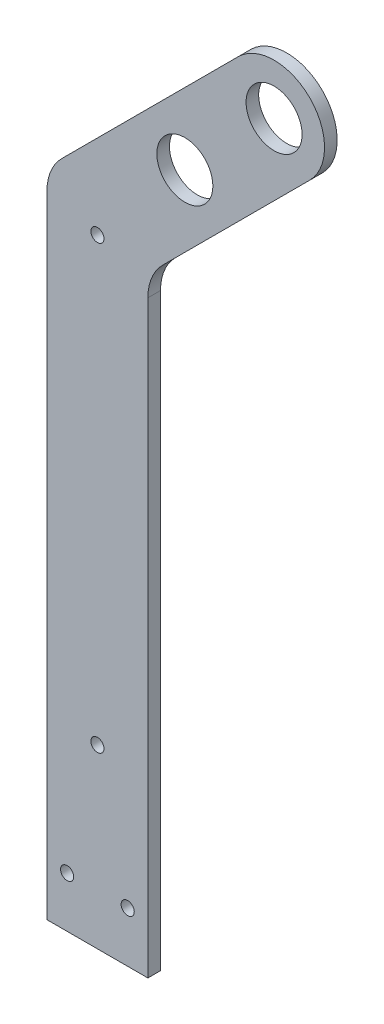
SolidWorks part; units mm, degrees
material "6061 合金"
ref_plane "前视基准面" through (0, 0, 0) normal (0, 0, 1) x (1, 0, 0)
ref_plane "上视基准面" through (0, 0, 0) normal (0, 1, 0) x (1, 0, 0)
ref_plane "右视基准面" through (0, 0, 0) normal (1, 0, 0) x (0, 0, -1)
other "Configuration Table"
sketch "草图1" plane through (0, 0, 0) normal (0, 0, 1) x (1, 0, 0)
  circle A0 centre (0, 0) radius 20
  circle A1 centre (0, 0) radius 11.1
  dimension "D1" = 40
  dimension "D2" = 22.2
extrude "凸台-拉伸1" add sketch "草图1" along normal blind 60 contours A1 | A0 region at (0, 0, 0)
ref_plane "基准面1" through (0, 0, 30) normal (0, 0, 1) x (1, 0, 0)
sketch "草图2" plane through (0, 0, 30) normal (0, 0, 1) x (1, 0, 0)
  line L0 (0, 0) -> (-70, -70) construction
  line L1 (-70, -70) -> (-70, -320) construction
  line L2 (0, -57.3148) -> (0, 49.9409) construction
  line L3 (-56.8582, 0) -> (46.4003, 0) construction
  line L4 (-14.1421, 14.1421) -> (-90, -61.7157)
  line L5 (14.1421, -14.1421) -> (-50, -78.2843)
  line L6 (-90, -61.7157) -> (-90, -320)
  line L7 (-50, -78.2843) -> (-50, -320)
  line L8 (-90, -320) -> (-50, -320)
  circle A2 centre (0, 0) radius 20 construction
  arc A3 (-14.1421, 14.1421) -> (14.1421, -14.1421) centre (0, 0) ccw
  dimension "D1" = 45
  dimension "D2" = 250
  dimension "D3" = 70
  dimension "D4" = 40
  dimension "D5" = 40
extrude "凸台-拉伸2" add sketch "草图2" along normal mid plane 60 contours L7 L8 L6 L4 A3 L5
sketch "草图4" plane through (0, 0, 60) normal (0, 0, 1) x (1, 0, 0)
  line L0 (-90, -61.7157) -> (-90, -320) construction
  line L1 (-90, -290) -> (-50, -290)
  line L2 (-90, -290) -> (-90, -350)
  line L4 (-50, -290) -> (-50, -350)
  line L5 (-50, -78.2843) -> (-50, -320) construction
  line L6 (-90, -320) -> (-50, -320) construction
  arc A0 (-90, -350) -> (-50, -350) centre (-70, -350) ccw
  circle A1 centre (-70, -350) radius 11
  dimension "D3" = 22
  dimension "D1" = 30
  dimension "D2" = 30
extrude "凸台-拉伸3" add sketch "草图4" along normal blind 5
mirror "镜向1" about plane through (0, 0, 30) normal (0, 0, 1) of "凸台-拉伸3"
sketch "草图5" plane through (0, 0, 0) normal (0, 1, 0) x (1, 0, 0)
  line L0 (0, 0) -> (0, -78.0582) construction
ref_plane "基准面2" through (-70, 0, 0) normal (-1, 0, 0) x (0, 0, 1)
sketch "草图7" plane through (-70, 0, 0) normal (-1, 0, 0) x (0, 0, 1)
  line L0 (-34.1239, -350) -> (109.535, -350) construction
sketch "草图8" plane through (0, 0, 60) normal (0, 0, 1) x (1, 0, 0)
  line L0 (0, 0) -> (-70, -70) construction
  circle A0 centre (-35.3553, -35.3553) radius 11.1
  dimension "D1" = 22.2
  dimension "D2" = 50
extrude "切除-拉伸1" cut sketch "草图8" against normal blind 100
fillet "圆角4" radius 20 2 edges at (-90, -61.7157, 30) (-50, -78.2843, 30)
fillet "圆角1" [suppressed] radius 50
fillet "圆角2" [suppressed] radius 3
sketch "草图9" plane through (0, 0, 65) normal (0, 0, 1) x (1, 0, 0)
  circle A0 centre (-70, -350) radius 13
  dimension "D1" = 26
extrude "切除-拉伸2" [suppressed] cut sketch "草图9" against normal blind 0.75
sketch "草图10" plane through (0, 0, -5) normal (0, 0, -1) x (-1, 0, 0)
  circle A0 centre (70, -350) radius 13
  dimension "D1" = 26
extrude "切除-拉伸3" [suppressed] cut sketch "草图10" against normal blind 0.75 contours A0
sketch "草图11" plane through (-90, 0, 0) normal (-1, 0, 0) x (0, 0, 1)
  circle A0 centre (48.5, -118.9949) radius 2.75
  circle A1 centre (48.5, -183.9949) radius 2.75
  circle A2 centre (48.5, -248.9949) radius 2.75
  circle A3 centre (11.5, -248.9949) radius 2.75
  circle A4 centre (11.5, -183.9949) radius 2.75
  circle A5 centre (11.5, -118.9949) radius 2.75
  dimension "D1" = 5.5
extrude "切除-拉伸4" [suppressed] cut sketch "草图11" against normal through all contours A1 | A2 | A0 | A3 | A4 | A5
sketch "草图12" [suppressed] plane through (-90, 0, 0) normal (-1, 0, 0) x (0, 0, 1)
  line L0 (30, -62.0134) -> (30, -339.6946) construction
  line L1 (10, -128.9949) -> (50, -128.9949)
  line L2 (10, -128.9949) -> (10, -173.9949)
  line L3 (10, -173.9949) -> (50, -173.9949)
  line L4 (50, -128.9949) -> (50, -173.9949)
  line L5 (10, -193.9949) -> (50, -193.9949)
  line L6 (10, -193.9949) -> (10, -238.9949)
  line L7 (10, -238.9949) -> (50, -238.9949)
  line L8 (50, -193.9949) -> (50, -238.9949)
  line L9 (10, -258.9949) -> (50, -258.9949)
  line L10 (10, -258.9949) -> (10, -290)
  line L11 (10, -290) -> (50, -290)
  line L12 (50, -258.9949) -> (50, -290)
  line L13 (19.5, -173.9949) -> (40.5, -173.9949)
  line L14 (19.5, -173.9949) -> (19.5, -193.9949)
  line L15 (19.5, -193.9949) -> (40.5, -193.9949)
  line L16 (40.5, -173.9949) -> (40.5, -193.9949)
  line L17 (19.5, -238.9949) -> (40.5, -238.9949)
  line L18 (19.5, -238.9949) -> (19.5, -258.9949)
  line L19 (19.5, -258.9949) -> (40.5, -258.9949)
  line L20 (40.5, -238.9949) -> (40.5, -258.9949)
  line L21 (60, -82.4264) -> (60, -290) construction
  line L22 (0, -290) -> (0, -82.4264) construction
  line L23 (57, -320) -> (3, -320) construction
  circle A0 centre (48.5, -118.9949) radius 2.75 construction
  circle A1 centre (48.5, -183.9949) radius 2.75 construction
  circle A2 centre (48.5, -248.9949) radius 2.75 construction
  dimension "D1" = 10
  dimension "D2" = 10
  dimension "D3" = 10
  dimension "D4" = 8
  dimension "D5" = 10
  dimension "D6" = 10
  dimension "D7" = 10
  dimension "D8" = 30
extrude "减重" [suppressed] cut sketch "草图12" against normal through all contours L0 L1 L2 L3 | L15 L0 L17 L7 L8 L5 | L0 L5 L6 L7 | L19 L0 L11 L12 L9 | L0 L9 L10 L11 | L1 L0 L13 L3 L4
fillet "圆角3" [suppressed] radius 3
sketch "草图13" plane through (0, 0, 60) normal (0, 0, 1) x (1, 0, 0)
  circle A0 centre (0, 0) radius 13
  circle A1 centre (-35.3553, -35.3553) radius 13
  dimension "D1" = 26
  dimension "D2" = 26
extrude "切除-拉伸6" [suppressed] cut sketch "草图13" against normal blind 1.75
sketch "草图14" plane through (0, 0, 0) normal (0, 0, -1) x (-1, 0, 0)
  circle A0 centre (0, 0) radius 13
  circle A1 centre (35.3553, -35.3553) radius 13
  dimension "D1" = 26
  dimension "D2" = 26
extrude "切除-拉伸7" [suppressed] cut sketch "草图14" against normal blind 1.75
sketch "草图15" [suppressed] plane through (0, 0, 0) normal (0, 0, -1) x (-1, 0, 0)
  line L0 (0, 0) -> (70, -350) construction
  line L1 (56.2719, -67.2005) -> (60.1942, -86.8121) construction
  line L2 (70, -350) -> (204.3541, -323.1292) construction
  circle A0 centre (56.2719, -67.2005) radius 2.75
  circle A1 centre (75.2172, -73.6095) radius 2.75
  circle A2 centre (60.1942, -86.8121) radius 2.75
  dimension "D1" = 5.5
  dimension "D2" = 20
  dimension "D3" = 20
  dimension "D4" = 20
  dimension "D5" = 42
  dimension "D6" = 270
extrude "切除-拉伸8" [suppressed] cut sketch "草图15" against normal through all contours A2 | A0 | A1
ref_plane "小腿主干连杆面" through (0, 0, 0) normal (0.9806, -0.1961, 0) x (0, 0, -1)
ref_plane "小腿主干对称面" through (0, 0, 30) normal (0, 0, -1) x (-1, 0, 0)
sketch "草图16" plane through (0, 0, 60) normal (0, 0, 1) x (1, 0, 0)
  line L0 (0, 0) -> (-70, -350)
  line L1 (-35.3553, -35.3553) -> (0, 0)
sketch "草图17" plane through (0, 0, 60) normal (0, 0, 1) x (1, 0, 0)
  line L0 (0, 0) -> (-70, -350) construction
  line L1 (118.6974, 32.5948) -> (32.9122, -396.3312) construction
  line L2 (92.7764, -97.0102) -> (20.2919, -82.5133)
  line L3 (73.1648, -195.0683) -> (0.6803, -180.5713)
  circle A0 centre (20.2919, -82.5133) radius 46
  circle A1 centre (0.6803, -180.5713) radius 46
  dimension "D3" = 92
  dimension "D4" = 92
  dimension "D1" = 110
  dimension "D2" = 73.92
  dimension "D5" = 180
  dimension "D6" = 280
sketch "草图18" plane through (0, 0, 60) normal (0, 0, 1) x (1, 0, 0)
  line L1 (14.1421, -14.1421) -> (-44.1421, -72.4264) construction
  line L3 (14.1421, -14.1421) -> (-44.1421, -72.4264)
  line L4 (15.4873, -12.6548) -> (52.8188, -49.9864)
  line L5 (-50, -128.5133) -> (20.2919, -128.5133)
  line L10 (-90, -290) -> (-50, -290)
  line L11 (-50, -290) -> (-50, -86.5685)
  line L12 (-44.1421, -72.4264) -> (14.1421, -14.1421)
  line L13 (-14.1421, 14.1421) -> (-84.1421, -55.8579)
  line L14 (-90, -70) -> (-90, -290)
  line L16 (-50, -128.5133) -> (-50, -86.5685)
  line L17 (-44.1421, -72.4264) -> (14.1421, -14.1421)
  circle A0 centre (20.2919, -82.5133) radius 46 construction
  arc A1 (14.1421, -14.1421) -> (-14.1421, 14.1421) centre (0, 0) ccw construction
  arc A2 (14.1421, -14.1421) -> (-14.1421, 14.1421) centre (0, 0) ccw
  arc A3 (14.1421, -14.1421) -> (15.4873, -12.6548) centre (0, 0) ccw
  arc A4 (20.2919, -128.5133) -> (52.8188, -49.9864) centre (20.2919, -82.5133) ccw
  circle A5 centre (20.2919, -82.5133) radius 35
  arc A9 (-84.1421, -55.8579) -> (-90, -70) centre (-70, -70) ccw
  arc A10 (-84.1421, -55.8579) -> (-90, -70) centre (-70, -70) ccw
  arc A11 (-44.1421, -72.4264) -> (-50, -86.5685) centre (-30, -86.5685) ccw
  arc A12 (-44.1421, -72.4264) -> (-50, -86.5685) centre (-30, -86.5685) ccw
  line M14 (-50, -290) -> (-50, -86.5685)
  line M15 (-44.1421, -72.4264) -> (14.1421, -14.1421)
  arc M16 (14.1421, -14.1421) -> (-14.1421, 14.1421) centre (0, 0) ccw
  arc M22 (-50, -86.5685) -> (-44.1421, -72.4264) centre (-30, -86.5685) cw
  dimension "D2" = 70
  dimension "D1" = 0
extrude "凸台-拉伸4" add sketch "草图18" against normal blind 5 from offset 25 contours L5 A4 L4 A5 M16 M15 M22 M14 region at (16.0508, -14.5165, 60) offset against normal yes
sketch "草图19" plane through (0, 0, 0) normal (0, 0, -1) x (-1, 0, 0)
  line L0 (50, -86.5685) -> (50, -290) construction
  line L1 (50, -134.5713) -> (50, -226.5713)
  line L2 (-0.6803, -134.5713) -> (50, -134.5713)
  line L3 (-0.6803, -226.5713) -> (50, -226.5713)
  circle A0 centre (-0.6803, -180.5713) radius 46 construction
  arc A1 (-0.6803, -134.5713) -> (-0.6803, -226.5713) centre (-0.6803, -180.5713) ccw
  circle A2 centre (-0.6803, -180.5713) radius 35
  dimension "D1" = 70
extrude "凸台-拉伸5" add sketch "草图19" against normal blind 5 from offset 25 offset against normal yes
fillet "圆角5" radius 10 2 edges at (-50, -226.5713, 27.5) (-50, -128.5133, 32.5)
sketch "草图21" plane through (0, 0, 65) normal (0, 0, 1) x (1, 0, 0)
  line L0 (-70, -350) -> (-70, -6.9331) construction
  circle A0 centre (-70, -75) radius 2.6
  circle A1 centre (-70, -250) radius 2.6
  circle A2 centre (-58, -300) radius 2.6
  circle A3 centre (-82, -300) radius 2.6
  dimension "D1" = 5.2
  dimension "D2" = 12
  dimension "D3" = 50
  dimension "D4" = 100
  dimension "D5" = 175
extrude "切除-拉伸9" cut sketch "草图21" against normal through all both and the other way through all
sketch "草图22" plane through (-90, 0, 0) normal (-1, 0, 0) x (0, 0, 1)
  line L0 (-5, -350) -> (-5, -370) construction
  line L5 (-5, -390.4661) -> (45, -390.4661)
  line L6 (-5, -390.4661) -> (-5, 64.9179)
  line L7 (-5, 64.9179) -> (45, 64.9179)
  line L8 (45, -390.4661) -> (45, 64.9179)
  line L10 (65, -370) -> (50, -370)
  line L11 (65, -370) -> (65, 61.088)
  line L12 (65, 61.088) -> (50, 61.088)
  line L13 (50, -370) -> (50, 61.088)
  dimension "D1" = 15
  dimension "D2" = 5
extrude "切除-拉伸10" cut sketch "草图22" against normal through all both contours L8 L7 L6 L5 | L13 L12 L11 L10
